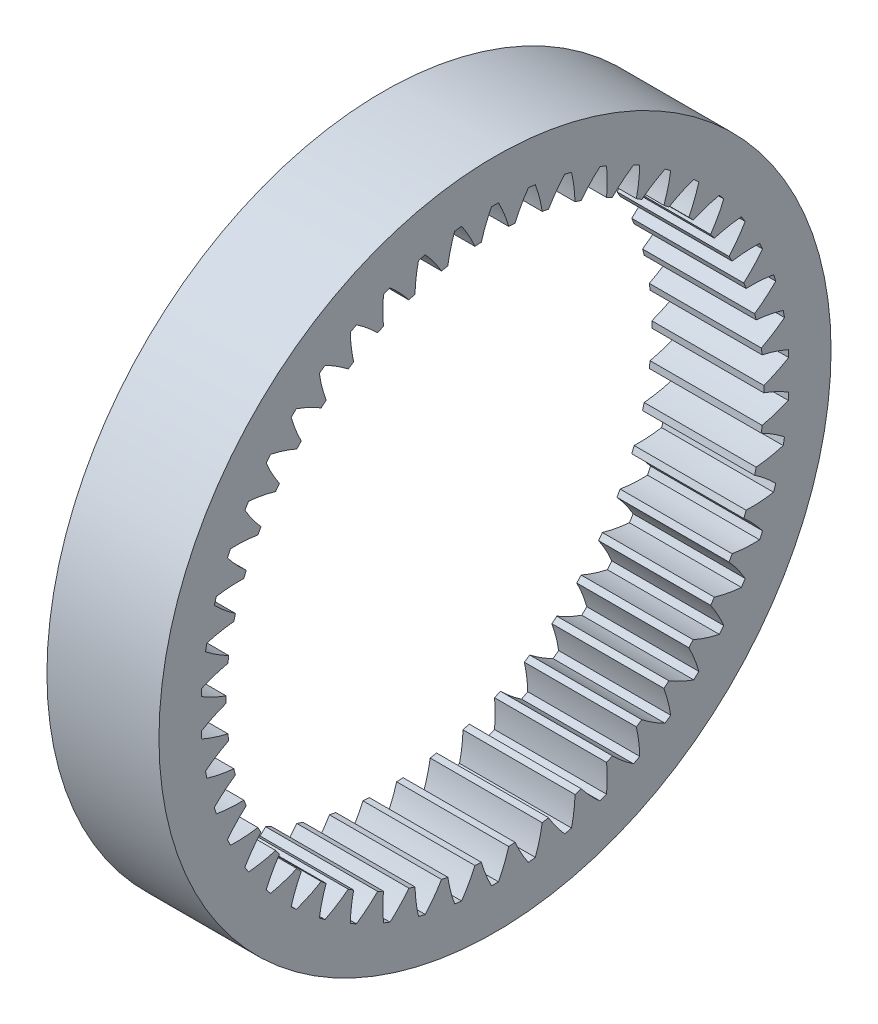
SolidWorks part; units mm, degrees
ref_plane "Plane1" through (0, 0, 0) normal (0, 0, 1) x (1, 0, 0)
ref_plane "Plane2" through (0, 0, 0) normal (0, 1, 0) x (1, 0, 0)
ref_plane "Plane3" through (0, 0, 0) normal (1, 0, 0) x (0, 0, -1)
other "Configuration Table"
sketch "HoldingSke" plane through (0, 0, 0) normal (0, 1, 0) x (1, 0, 0)
  line L0 (0, 0) -> (0.6428, -0.766)
  line L1 (-15, 0) -> (100, 0) construction
  line L2 (0, 0) -> (-2.1039, 2.3779)
  line L3 (0, 0) -> (-11.863, 4.5341)
  line L4 (0, 0) -> (5.5511, 6.6156)
  line L5 (0, 0) -> (-23.7986, -8.8762)
  line L6 (0, 0) -> (-10.5278, -7.1032)
  line L7 (-2.1039, 2.3779) -> (3.3635, 27.1825)
  line L8 (-76.2, 3.3779) -> (-54.61, 3.3779)
  line L9 (-71.009, 38.7566) -> (-53.1078, 45.2721)
  line L10 (-76.2, 71.12) -> (104.1128, 71.12)
  line L11 (0, 0) -> (-10, 0)
  line L12 (-76.2, 101.6) -> (-76.162, 101.6)
  line L13 (24.9733, 27.94) -> (52.9518, 28.4284)
  line L14 (24.9733, 27.94) -> (24.9743, 27.94)
  line L15 (24.9733, 27.94) -> (100.4006, 29.5858)
  circle A0 centre (0, 0) radius 30
  circle A1 centre (0, 0) radius 12.7
  circle A2 centre (0, 0) radius 12.7
  dimension "Num_teeth" = 50
  dimension "Pitch_radius" = 180.3128
  dimension "Width" = 10
  dimension "Diameter" = 60
sketch "BasProSke" plane through (0, 0, 0) normal (0, 1, 0) x (1, 0, 0)
  line L0 (-10, 0) -> (60, 0) construction
  line L1 (0, 24) -> (0, 30)
  line L2 (0, 24) -> (10, 24)
  line L3 (10, 24) -> (10, 30)
  line L4 (10, 30) -> (0, 30)
  dimension "Thickness" = 10
  dimension "Diameter" = 60
revolve "Base-Revolve" add sketch "BasProSke" angle 360 about L0
sketch "TooCutSke" plane through (0, 0, 0) normal (1, 0, 0) x (0, 0, -1)
  line L3 (0.8803, 24.9845) -> (0.8803, 53.6633) construction
  line L4 (0, 0) -> (0, 59.563) construction
  line L5 (0, 0) -> (-4.2903, 68.1927) construction
  line L6 (-10.7899, 20.506) -> (36.4405, 23.4775) construction
  circle A0 centre (0, 0) radius 25 construction
  circle A1 centre (0, 0) radius 26.251 construction
  circle A2 centre (0, 0) radius 21.1431 construction
  circle A3 centre (0, 0) radius 23.9746 construction
  arc A4 (1.2282, 23.9431) -> (0.3126, 26.2491) centre (-10.7899, 20.506) ccw
  arc A5 (1.2282, 23.9431) -> (-1.2282, 23.9431) centre (0, 0) ccw
  arc A6 (0.3126, 26.2491) -> (-0.3126, 26.2491) centre (0, 0) ccw
  arc A7 (-0.3126, 26.2491) -> (-1.2282, 23.9431) centre (10.7899, 20.506) ccw
extrude "ToothCut" cut sketch "TooCutSke" along normal through all
fillet "Breaks" [suppressed] radius 0.1
fillet "RootFillets" [suppressed] radius 0.251
pattern_circular "TeethCuts" count 50 every 7.2 about axis through (-10, 0, 0) along (1, 0, 0) of "RootFillets", "Breaks", "ToothCut"
equation "' \"Module@HoldingSke\" = 6.35"
equation "' \"Num_teeth@HoldingSke\" = 24"
equation "' \"Ap@HoldingSke\" =  14.5"
equation "' \"Ap@HoldingSke\" = 14.5"
equation "' \"Width@HoldingSke\" = 12"
equation "' \"Diameter@HoldingSke\" = 8 * 25.4"
equation "' \"Show_teeth@HoldingSke\" = 100"
equation "' \"Backlash@HoldingSke\" = 0.009 * 25.4"
equation "' \"Addendum_fac@HoldingSke\" = 1.0"
equation "' \"Dedendum_fac@HoldingSke\" = 1.25"
equation "' \"Dedendum_add@HoldingSke\" = 0.00005 * 25.4"
equation "' \"Clearance_fac@HoldingSke\" = 0.25"
equation "\"Pitch@HoldingSke\" = 1 / \"Module@HoldingSke\" "
equation "\"Overcut_dia@TooCutSke\" = (\"Num_teeth@HoldingSke\" - 2 * \"Addendum_fac@HoldingSke\") / \"Pitch@HoldingSke\" - 0.002 * 25.4"
equation "\"Pitch_dia@TooCutSke\" = \"Num_teeth@HoldingSke\" / \"Pitch@HoldingSke\""
equation "\"Base_dia@TooCutSke\" = \"Num_teeth@HoldingSke\" / \"Pitch@HoldingSke\" * cos((\"Ap@HoldingSke\"  * 3.14159265 / 180)) * 0.90"
equation "\"Root_dia@TooCutSke\" = \"Num_teeth@HoldingSke\"  / \"Pitch@HoldingSke\" + 2 *  \"Dedendum_fac@HoldingSke\"/ \"Pitch@HoldingSke\" + \"Dedendum_add@HoldingSke\" * 2"
equation "\"Half_ang@TooCutSke\" = 180 / \"Num_teeth@HoldingSke\""
equation "\"Half_CT@TooCutSke\" = \"Num_teeth@HoldingSke\" / \"Pitch@HoldingSke\" * sin((3.14159265 / 2 / \"Num_teeth@HoldingSke\")) / 2 + 10 * \"Backlash@HoldingSke\" / 4"
equation "\"Flank_rad@TooCutSke\" = \"Num_teeth@HoldingSke\" / \"Pitch@HoldingSke\" / 4"
equation "\"Radius@RootFillets\"= \"Clearance_fac@HoldingSke\" / \"Pitch@HoldingSke\" + \"Dedendum_add@HoldingSke\""
equation "\"Break_rad@Breaks\" = 0.02 / \"Pitch@HoldingSke\" * 5"
equation "\"Num_teeth@TeethCuts\" = int( \"Show_teeth@HoldingSke\" ) + 1"
equation "\"Num_teeth@TeethCuts\" = ((sgn( \"Num_teeth@TeethCuts\" - \"Num_teeth@HoldingSke\" )-1)*( \"Num_teeth@TeethCuts\" - \"Num_teeth@HoldingSke\" ))/-2+ \"Num_teeth@HoldingSke\""
equation "\"Num_teeth@TeethCuts\" = ((sgn( \"Num_teeth@TeethCuts\" - 2.0)+1)*( \"Num_teeth@TeethCuts\" - 2.0))/2 +2.0"
equation "\"Angle@TeethCuts\" = 360.0 / \"Num_teeth@HoldingSke\""
equation "\"Diameter@BasProSke\" = \"Num_teeth@HoldingSke\"  / \"Pitch@HoldingSke\" + 2 *  \"Dedendum_fac@HoldingSke\"/ \"Pitch@HoldingSke\" + \"Dedendum_add@HoldingSke\" * 2 + 0.002 * 25.4"
equation "\"Diameter@BasProSke\" = ((sgn( \"Diameter@BasProSke\"  - \"Diameter@HoldingSke\" )+1)*( \"Diameter@BasProSke\"  - \"Diameter@HoldingSke\" ))/2 + \"Diameter@HoldingSke\""
equation "\"Inside_diameter@BasProSke\" =  (\"Num_teeth@HoldingSke\" - 2 * \"Addendum_fac@HoldingSke\") / \"Pitch@HoldingSke\" "
equation "\"Thickness@BasProSke\"  = \"Width@HoldingSke\""
